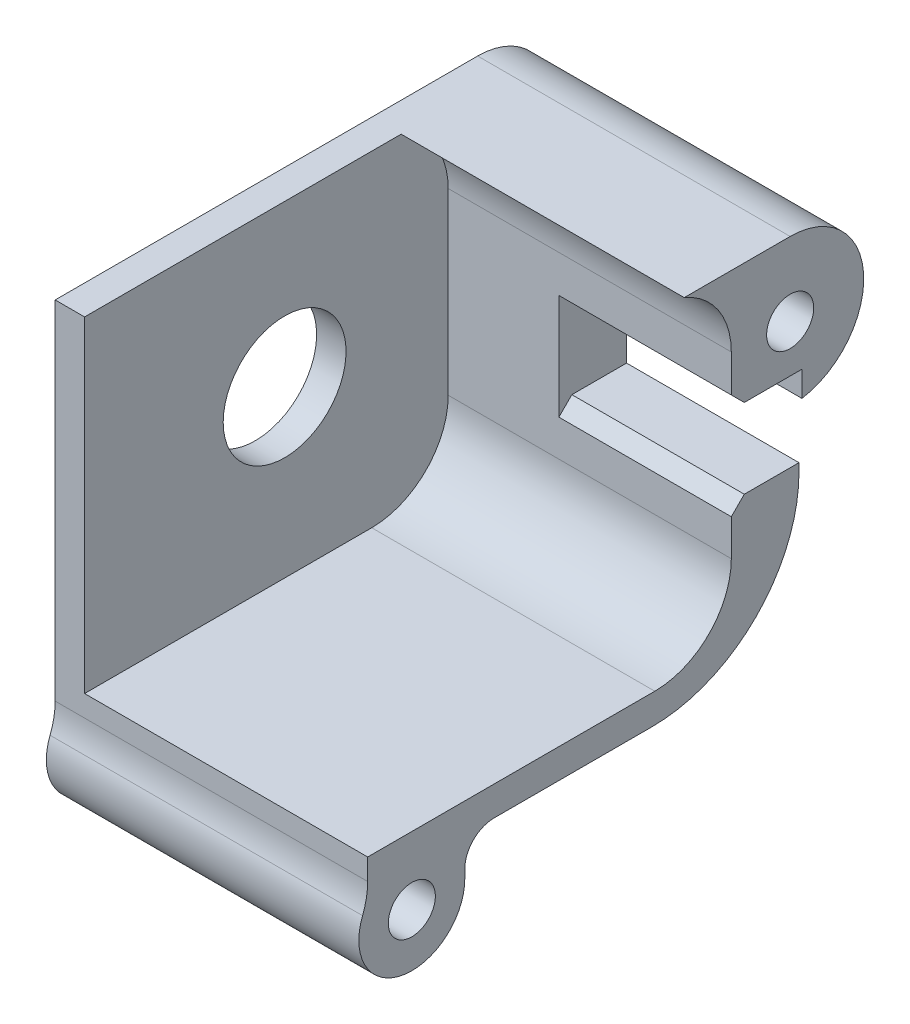
SolidWorks part; units mm, degrees
note: The reader was unsure of these and kept them because the rebuilt part matched: shared geometry of "Sketch1<7>", "Sketch1<8>".
ref_plane "Front Plane" through (0, 0, 0) normal (0, 0, 1) x (1, 0, 0)
ref_plane "Top Plane" through (0, 0, 0) normal (0, 1, 0) x (1, 0, 0)
ref_plane "Right Plane" through (0, 0, 0) normal (1, 0, 0) x (0, 0, -1)
ref_plane "Plane1" through (-6542.3816, 0, 0) normal (1, 0, 0) x (0, 0, -1)
sketch "Sketch1" plane through (-6551.3017, 0, 0) normal (1, 0, 0) x (0, 0, -1)
  line L0 (763.7522, -3111.4269) -> (763.7522, -3135.0389)
  line L1 (789.35, -3119.6419) -> (793.2672, -3119.6419)
  line L2 (772.3522, -3135.5948) -> (783.0672, -3135.5948)
  line L3 (793.0672, -3125.5948) -> (793.0672, -3121.3908)
  line L4 (792.4672, -3111.4269) -> (763.7522, -3111.4269)
  line L5 (793.0672, -3124.8419) -> (793.0672, -3119.8419) construction
  line L6 (783.2672, -3133.3948) -> (751.2672, -3133.3948) construction
  line L7 (783.2672, -3133.5948) -> (763.7522, -3133.5948)
  line L8 (788.4672, -3128.3948) -> (788.4672, -3116.2269)
  line L9 (788.4672, -3118.7591) -> (789.35, -3119.6419)
  line L10 (793.2672, -3119.6419) -> (793.2672, -3121.3625)
  line L11 (788.4672, -3125.9248) -> (789.35, -3125.0419)
  line L12 (789.35, -3125.0419) -> (793.0672, -3125.0419)
  line L13 (788.4672, -3122.3419) -> (793.0672, -3122.3419) construction
  line L14 (770.3522, -3138.1948) -> (770.3522, -3137.5948)
  line L15 (789.2672, -3124.8419) -> (788.2672, -3125.8419) construction
  line L16 (788.2672, -3118.8419) -> (789.2672, -3119.8419) construction
  line L17 (751.2672, -3111.2269) -> (783.2672, -3111.2269) construction
  line L18 (793.0672, -3119.8419) -> (789.2672, -3119.8419) construction
  arc A0 (783.0672, -3135.5948) -> (793.0672, -3125.5948) centre (783.0672, -3125.5948) ccw
  circle A2 centre (766.0972, -3122.3419) radius 1.995
  circle A3 centre (777.3472, -3122.3419) radius 4.175
  circle A4 centre (766.0972, -3122.3419) radius 1.845 construction
  circle A5 centre (766.0972, -3122.3419) radius 1.845 construction
  arc A7 (788.2672, -3116.2269) -> (783.2672, -3111.2269) centre (783.2672, -3116.2269) ccw construction
  circle A8 centre (790.6672, -3122.3419) radius 1.38 construction
  circle A10 centre (766.7522, -3138.1948) radius 1.6
  arc A11 (783.2672, -3133.5948) -> (788.4672, -3128.3948) centre (783.2672, -3128.3948) ccw
  arc A12 (788.4672, -3116.2269) -> (785.2672, -3111.4269) centre (783.2672, -3116.2269) ccw
  arc A13 (783.2672, -3133.3948) -> (788.2672, -3128.3948) centre (783.2672, -3128.3948) ccw construction
  circle A14 centre (777.3472, -3122.3419) radius 3.675 construction
  circle A15 centre (792.4672, -3116.4269) radius 1.6
  circle A16 centre (792.4672, -3116.4269) radius 5
  arc A18 (763.4033, -3136.8737) -> (770.3522, -3138.1948) centre (766.7522, -3138.1948) ccw
  arc A19 (770.3522, -3137.5948) -> (772.3522, -3135.5948) centre (772.3522, -3137.5948) cw
  arc A20 (763.4033, -3136.8737) -> (763.7522, -3135.0389) centre (758.7522, -3135.0389) ccw
  point P14 (764.2522, -3122.3419)
  point P28 (766.7522, -3136.5948)
  point P29 (766.7522, -3139.7948)
  dimension "D1" = 0.5
  dimension "D2" = 10
  dimension "D3" = 3.2
  dimension "D7" = 2
  dimension "D8" = 0.2
  dimension "D11" = 0.15
  dimension "D13" = 0.5
  dimension "D14" = 4
  dimension "D15" = 10
  dimension "D17" = 2
  dimension "D18" = 5
  dimension "D4" = 3
  dimension "D5" = 2
  dimension "D6" = 3
  dimension "D9" = 0.2
  dimension "D10" = 0.2
  dimension "D12" = 0.2
  dimension "D16" = 0.2
extrude "Boss-Extrude1" add sketch "Sketch1" along normal offset from surface (7.52 mm away) 0.2 from offset 0.2
extrude "Boss-Extrude2" add sketch "Sketch1<7>" against normal blind 2 from surface at -0.2
sketch "Sketch1<7>" plane through (-6551.3017, 0, 0) normal (1, 0, 0) x (0, 0, -1) same geometry as "Sketch1"
extrude "Boss-Extrude3" add sketch "Sketch1<8>" along normal offset from surface (11.72 mm away) 1.2 from surface at 7.32 starting at face at (-6543.9816, -3116.4269, -794.0672)
sketch "Sketch1<8>" plane through (-6551.3017, 0, 0) normal (1, 0, 0) x (0, 0, -1) same geometry as "Sketch1"
